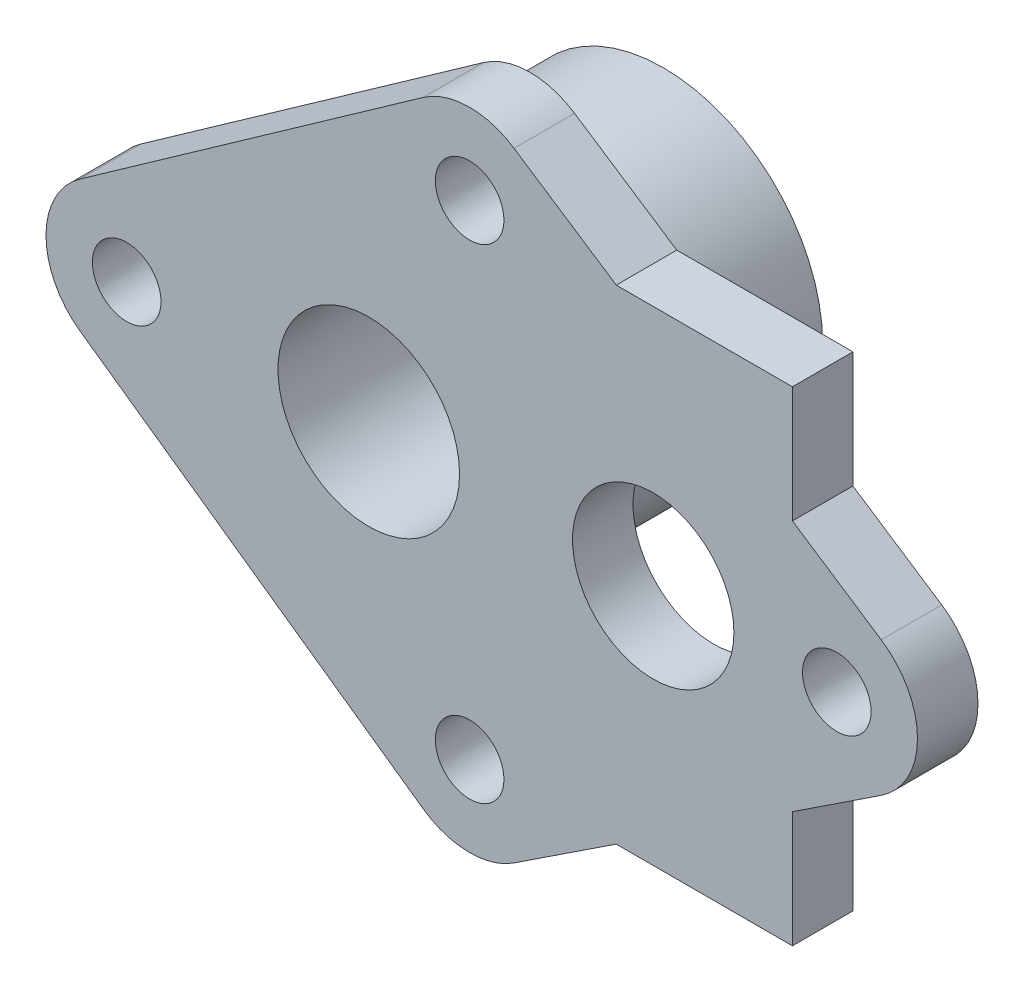
SolidWorks part; units mm, degrees
ref_plane "Płaszczyzna przednia" through (0, 0, 0) normal (0, 0, 1) x (1, 0, 0)
ref_plane "Płaszczyzna górna" through (0, 0, 0) normal (0, 1, 0) x (1, 0, 0)
ref_plane "Płaszczyzna prawa" through (0, 0, 0) normal (1, 0, 0) x (0, 0, -1)
sketch "Szkic1" plane through (0, 0, 0) normal (0, 0, 1) x (1, 0, 0)
  circle A0 centre (0, 0) radius 4.75
  circle A1 centre (0, 0) radius 7.9
  dimension "D1" = 9.5
  dimension "D2" = 15.8
extrude "Dodanie-wyciągnięcie1" add sketch "Szkic1" along normal blind 11.6
sketch "Szkic2" plane through (0, 0, 11.6) normal (0, 0, 1) x (1, 0, 0)
  circle A0 centre (0, 0) radius 4.5
  circle M2 centre (0, 0) radius 4.75
extrude "Dodanie-wyciągnięcie2" add sketch "Szkic2" against normal blind 0.5 contours A0 M2 region at (-4.6156, 0, 11.6)
chamfer "Sfazowanie1" distance 11.5 distance2 0.5 1 edges at (4.75, 0, 11.1) first distance on face at (4.75, 0, 0)
sketch "Szkic4" plane through (0, 0, 11.6) normal (0, 0, 1) x (1, 0, 0)
  line L0 (-14.3067, 3.2679) -> (2.6933, 15.2679)
  line L1 (7.2018, 15.3394) -> (25.4018, 3.3394)
  line L2 (25.4018, -3.3394) -> (7.2018, -15.3394)
  line L3 (2.6933, -15.2679) -> (-14.3067, -3.2679)
  circle A0 centre (5, 12) radius 1.7
  circle A1 centre (5, -12) radius 1.7
  circle A2 centre (23.2, 0) radius 1.7
  circle A3 centre (-12, 0) radius 1.7
  circle A4 centre (-12, 0) radius 4
  circle A5 centre (5, 12) radius 4
  circle A6 centre (23.2, 0) radius 4
  circle A7 centre (5, -12) radius 4
  circle A8 centre (14.1, 0) radius 4
  point P23 (0, 0)
  circle M3 centre (0, 0) radius 7.9
  circle M4 centre (0, 0) radius 4.5
  dimension "D1" = 3.4
  dimension "D2" = 24
  dimension "D7" = 8
  dimension "D8" = 9.1
  dimension "D9" = 8
  dimension "D3" = 12
  dimension "D4" = 17
  dimension "D5" = 35.2
  dimension "D6" = 12
extrude "Dodanie-wyciągnięcie4" add sketch "Szkic4" along normal blind 3 contours A7 L2 A6 L1 A5 L0 A4 L3 M3 | A4 A3 M3 | A5 A0 | A7 A1 | A4 M3 M4 | A4 M3 | A2 | A6 region at (-5.5174, 8.8579, 11.6) region at (-10.2118, 3.4511, 11.6) region at (4.9383, 15.8864, 11.6) region at (3.2118, -8.5489, 11.6) region at (23.2, 0, 11.6) region at (-7.6766, 0, 11.6)
sketch "Szkic5" plane through (0, 0, 14.6) normal (0, 0, 1) x (1, 0, 0)
  line L0 (12.2667, 12) -> (21, 12)
  line L1 (7.2018, 15.3394) -> (25.4018, 3.3394) construction
  line L2 (21, 12) -> (21, 6.2418)
  line L3 (21, -6.2418) -> (21, -12)
  line L4 (25.4018, -3.3394) -> (7.2018, -15.3394) construction
  line L5 (21, -12) -> (12.2667, -12)
  line L6 (7.2018, 15.3394) -> (25.4018, 3.3394)
  line L7 (25.4018, -3.3394) -> (7.2018, -15.3394)
  circle A0 centre (5, -12) radius 1.7 construction
  line M5 (7.2018, -15.3394) -> (25.4018, -3.3394)
  line M7 (25.4018, 3.3394) -> (7.2018, 15.3394)
  dimension "D1" = 16
extrude "Dodanie-wyciągnięcie5" add sketch "Szkic5" against normal blind 3 contours L5 L3 M5 | L2 L0 M7 region at (18.0889, 10.0806, 14.6) region at (18.0889, -10.0806, 14.6)
